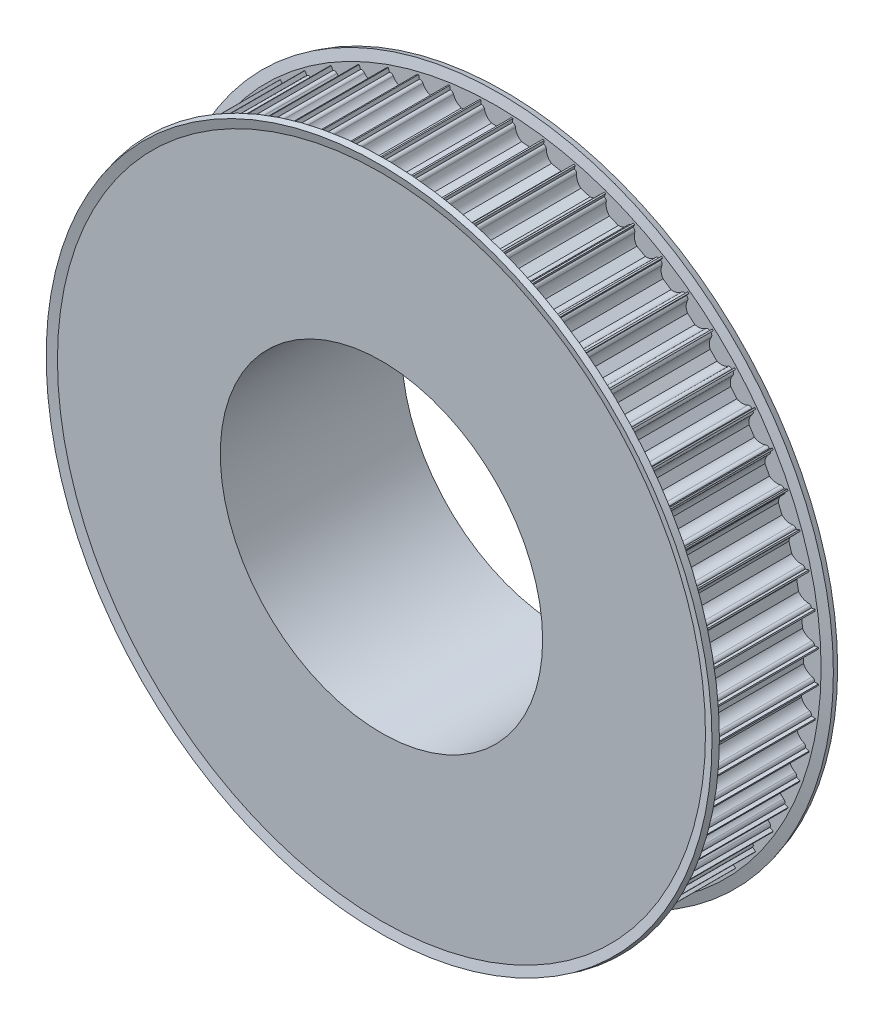
SolidWorks part; units mm, degrees
ref_plane "Front Plane" through (0, 0, 0) normal (0, 0, 1) x (1, 0, 0)
ref_plane "Top Plane" through (0, 0, 0) normal (0, 1, 0) x (1, 0, 0)
ref_plane "Right Plane" through (0, 0, 0) normal (1, 0, 0) x (0, 0, -1)
sketch "Sketch1" plane through (0, 0, 0) normal (1, 0, 0) x (0, 0, -1)
  line L0 (0, 0) -> (57.2771, 0) construction
  line L1 (0, 40) -> (45, 40)
  line L2 (45, 40) -> (45, 55.5)
  line L3 (45, 55.5) -> (30, 55.5)
  line L4 (30, 55.5) -> (30, 80)
  line L5 (30, 80) -> (0, 80)
  line L6 (0, 80) -> (0, 40)
  dimension "D1" = 15.5
  dimension "D2" = 15
  dimension "D3" = 30
  dimension "D4" = 40
  dimension "D5" = 80
revolve "Revolve1" add sketch "Sketch1" angle 360 about L0
sketch "Sketch2" plane through (0, 0, 0) normal (0, 0, 1) x (1, 0, 0)
  line L0 (-3.6742, 79) -> (-3.75, 79)
  line L1 (-3.75, 79) -> (-3.75, 81)
  line L2 (-3.75, 81) -> (3.75, 81)
  line L3 (3.75, 81) -> (3.75, 79)
  line L4 (3.75, 79) -> (3.6742, 79)
  line L5 (-1.199, 76.25) -> (1.199, 76.25)
  arc A0 (2.9394, 78.4) -> (1.199, 76.25) centre (0, 79) cw
  arc A1 (2.9394, 78.4) -> (3.6742, 79) centre (3.6742, 78.25) cw
  arc A2 (-2.9394, 78.4) -> (-3.6742, 79) centre (-3.6742, 78.25) ccw
  arc A3 (-1.199, 76.25) -> (-2.9394, 78.4) centre (0, 79) cw
  point P12 (3, 79)
  point P15 (-3, 79)
  dimension "D1" = 3
  dimension "D5" = 0.75
  dimension "D2" = 79
  dimension "D3" = 7.5
  dimension "D4" = 2
  dimension "D6" = 2.75
extrude "Cut-Extrude1" cut sketch "Sketch2" against normal up to next
pattern_circular "CirPattern1" count 64 over 360 about axis through (0, 0, 0) along (0, 0, 1) of "Cut-Extrude1"
sketch "Sketch3" plane through (0, 0, 0) normal (1, 0, 0) x (0, 0, -1)
  line L0 (15, -40.4807) -> (15, -4.9005) construction
  line L1 (30, -40.4807) -> (0, -40.4807) construction
  line L2 (30, 55.5) -> (30, 80.4125)
  line L3 (30, 80.4125) -> (30.592, 82.6218)
  line L4 (30.592, 82.6218) -> (29.1431, 83.01)
  line L5 (29.1431, 83.01) -> (28.5, 80.61)
  line L6 (28.5, 80.61) -> (28.5, 55.5)
  line L7 (28.5, 55.5) -> (30, 55.5)
  line L8 (45, 55.5) -> (30, 55.5) construction
  line L9 (1.5, 80.61) -> (1.5, 55.5)
  line L10 (0.8569, 83.01) -> (1.5, 80.61)
  line L11 (-0.592, 82.6218) -> (0.8569, 83.01)
  line L12 (0, 80.4125) -> (-0.592, 82.6218)
  line L13 (0, 55.5) -> (0, 80.4125)
  line L14 (1.5, 55.5) -> (0, 55.5)
  line L15 (-85.5417, 0) -> (504.8473, 0) construction
  dimension "D1" = 15
  dimension "D2" = 25.11
  dimension "D3" = 2.4
  dimension "D4" = 1.5
revolve "Revolve2" add sketch "Sketch3" angle 360 about L15
